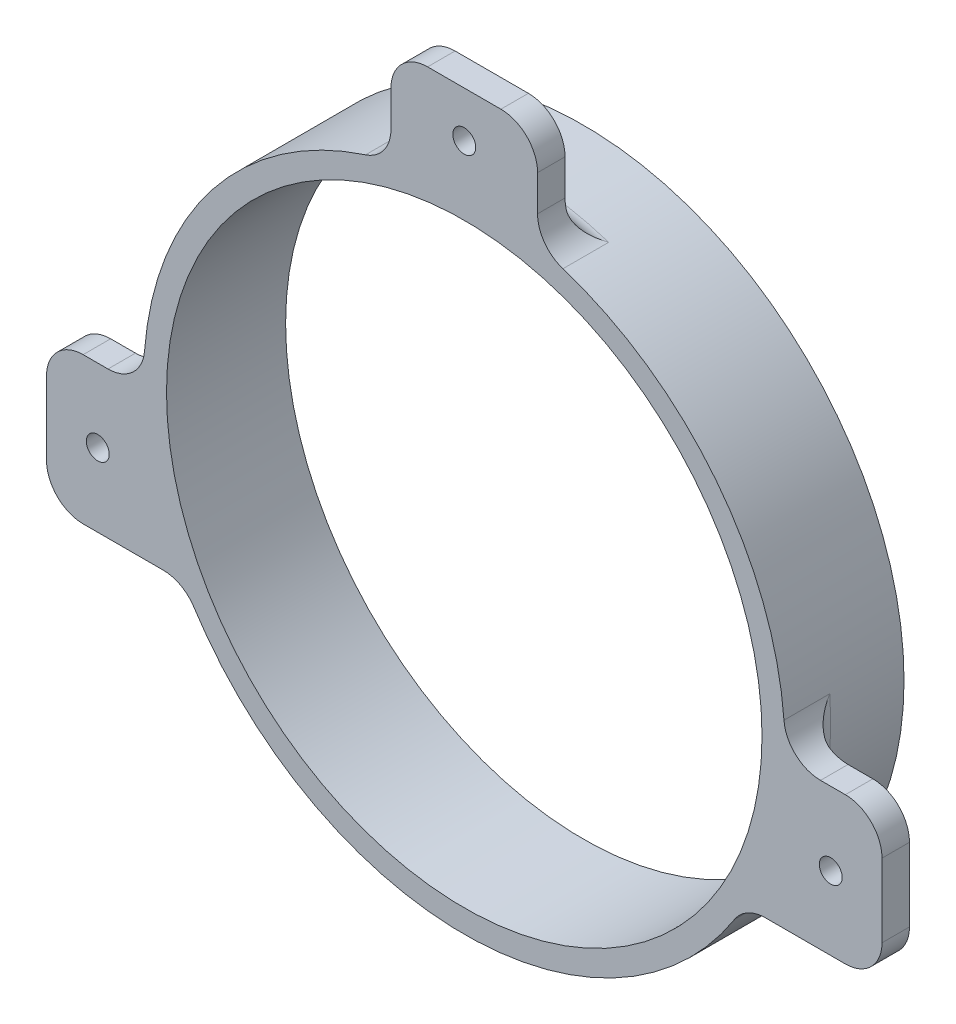
SolidWorks part; units mm, degrees
ref_plane "前视基准面" through (0, 0, 0) normal (0, 0, 1) x (1, 0, 0)
ref_plane "上视基准面" through (0, 0, 0) normal (0, 1, 0) x (1, 0, 0)
ref_plane "右视基准面" through (0, 0, 0) normal (1, 0, 0) x (0, 0, -1)
sketch "草图1" plane through (0, 0, 0) normal (0, 0, 1) x (1, 0, 0)
  circle A0 centre (0, 0) radius 35
  dimension "D1" = 70
extrude "凸台-拉伸1" add sketch "草图1" along normal blind 13
sketch "草图2" plane through (0, 0, 13) normal (0, 0, 1) x (1, 0, 0)
  line L0 (0, 0) -> (0, 35) construction
  line L1 (-8, 34.0735) -> (-8, 45)
  line L2 (-8, 45) -> (8, 45)
  line L3 (8, 45) -> (8, 34.0735)
  circle A0 centre (0, 0) radius 35 construction
  arc A1 (-8, 34.0735) -> (8, 34.0735) centre (0, 0) cw
  dimension "D4" = 35
  dimension "D1" = 8
  dimension "D2" = 8
  dimension "D3" = 10
extrude "凸台-拉伸2" add sketch "草图2" against normal blind 3
sketch "草图4" plane through (0, 0, 13) normal (0, 0, 1) x (1, 0, 0)
  line L0 (0, 45) -> (0, -35) construction
  line L1 (8, 45) -> (-8, 45) construction
  line L2 (-30.5941, -17) -> (-45.5941, -17)
  line L3 (-45.5941, -17) -> (-45.5941, -1)
  line L4 (-45.5941, -1) -> (-34.9857, -1)
  line L5 (45.5941, -1) -> (34.9857, -1)
  line L6 (45.5941, -17) -> (45.5941, -1)
  line L7 (30.5941, -17) -> (45.5941, -17)
  arc A0 (-8, 34.0735) -> (8, 34.0735) centre (0, 0) ccw construction
  arc A1 (-34.9857, -1) -> (-30.5941, -17) centre (0, 0) ccw
  arc A2 (34.9857, -1) -> (30.5941, -17) centre (0, 0) cw
  dimension "D4" = 35
  dimension "D1" = 17
  dimension "D2" = 16
  dimension "D3" = 15
extrude "凸台-拉伸3" add sketch "草图4" against normal blind 3
sketch "草图5" plane through (0, 0, 0) normal (0, 0, -1) x (-1, 0, 0)
  circle A0 centre (0, 0) radius 32.5
  dimension "D1" = 65
extrude "切除-拉伸1" cut sketch "草图5" against normal through all
fillet "圆角1" radius 4 12 edges at (8, 34.0735, 11.5) (8, 45, 11.5) (-8, 45, 11.5) (-8, 34.0735, 11.5) (-34.9857, -1, 11.5) (-45.5941, -1, 11.5) (-45.5941, -17, 11.5) (-30.5941, -17, 11.5) (45.5941, -1, 11.5) (45.5941, -17, 11.5) (30.5941, -17, 11.5) (34.9857, -1, 11.5)
fillet "圆角2" radius 2 3 edges at (33.948, -8.5168, 10) (0, 35, 10) (-33.948, -8.5168, 10)
sketch "草图6" plane through (0, 0, 13) normal (0, 0, 1) x (1, 0, 0)
  line L0 (0, 45) -> (0, 32.5) construction
  line L1 (4, 45) -> (-4, 45) construction
  circle A0 centre (0, 0) radius 32.5 construction
  circle A1 centre (0, 40) radius 1.25
  dimension "D2" = 2.5
  dimension "D1" = 40
extrude "切除-拉伸2" cut sketch "草图6" against normal through all
sketch "草图7" plane through (0, 0, 13) normal (0, 0, 1) x (1, 0, 0)
  line L0 (0, 45) -> (0, -35) construction
  line L1 (4, 45) -> (-4, 45) construction
  arc A0 (-29.4928, -18.8462) -> (29.4928, -18.8462) centre (0, 0) ccw construction
  circle A1 centre (-40, -9) radius 1.25
  circle A2 centre (40, -9) radius 1.25
  dimension "D3" = 2.5
  dimension "D1" = 40
  dimension "D2" = 9
extrude "切除-拉伸3" cut sketch "草图7" against normal through all
